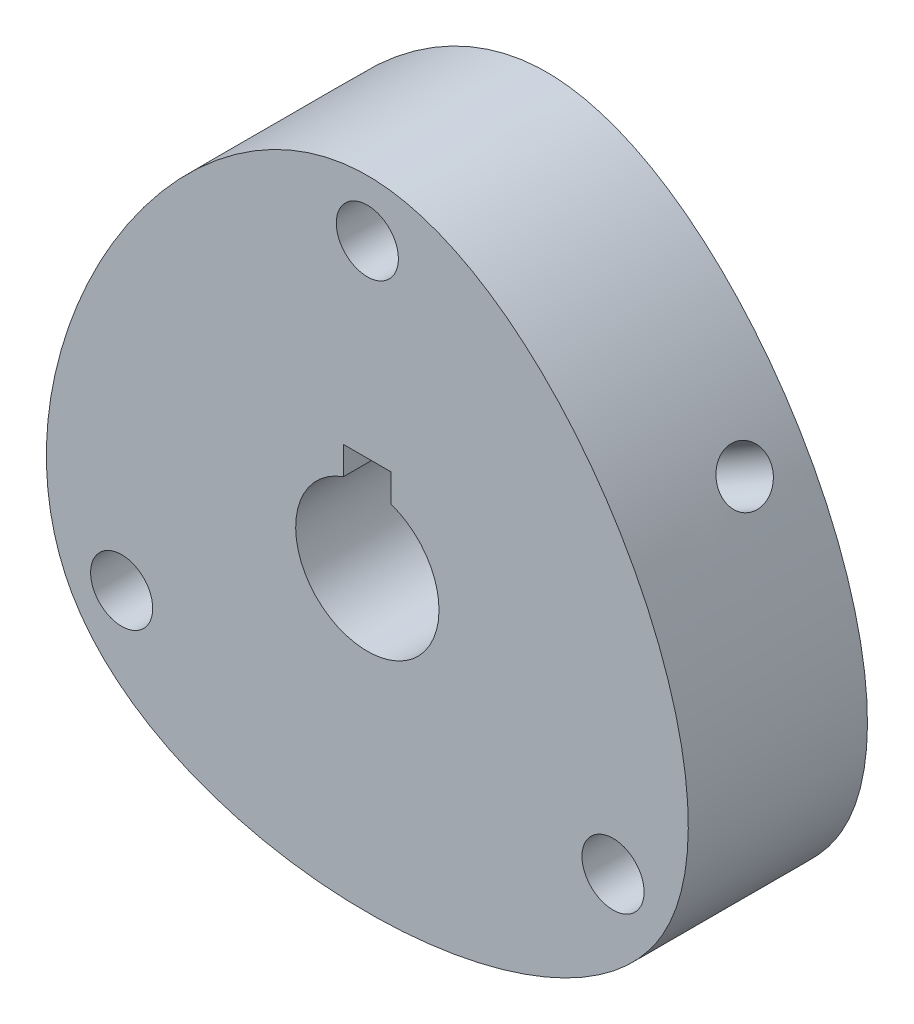
SolidWorks part; units mm, degrees
ref_plane "正面" through (0, 0, 0) normal (0, 0, 1) x (1, 0, 0)
ref_plane "平面" through (0, 0, 0) normal (0, 1, 0) x (1, 0, 0)
ref_plane "右側面" through (0, 0, 0) normal (1, 0, 0) x (0, 0, -1)
sketch "ｽｹｯﾁ1" plane through (0, 0, 0) normal (0, 0, 1) x (1, 0, 0)
  line L0 (0, 0) -> (-20.5681, -11.875) construction
  line L1 (0, 23.75) -> (-20.5681, -11.875) construction
  line L2 (-20.5681, -11.875) -> (20.5681, -11.875) construction
  line L3 (20.5681, -11.875) -> (0, 23.75) construction
  line L14 (-2, 4) -> (2, 4)
  line L15 (-2, 4) -> (-2, 8)
  line L16 (-2, 8) -> (2, 8)
  line L17 (2, 4) -> (2, 8)
  line L18 (-2, 4) -> (2, 8) construction
  line L19 (-2, 8) -> (2, 4) construction
  circle A0 centre (0, 0) radius 11.875 construction
  circle A1 centre (0, 23.75) radius 2.6
  circle A2 centre (20.5681, -11.875) radius 2.6
  circle A3 centre (-20.5681, -11.875) radius 2.6
  circle A4 centre (0, 0) radius 6
  circle A5 centre (0, 0) radius 28.5 construction
  ellipse E0 centre (20.5681, -11.875) end of major axis (23.0681, -7.5449) minor radius 4.75
  ellipse E1 centre (-20.5681, -11.875) end of major axis (-18.0681, -16.2051) minor radius 4.75
  ellipse E2 centre (0, 23.75) end of major axis (5, 23.75) minor radius 4.75
  spline S1 degree 3 poles (-49.3634, -28.5) (49.3634, -28.5) (0, 57) (-49.3634, -28.5) (49.3634, -28.5) (0, 57) knots -1 -0.666667 -0.333333 0 0.333333 0.666667 1 1.333333 1.666667 2 only from (24.6817, -14.25) to (24.6817, -14.25)
  point P26 (0, -5.7735)
  point P31 (0, 6)
  dimension "D1" = 5.2
  dimension "D2" = 5.2
  dimension "D3" = 5.2
  dimension "D5" = 12
  dimension "D6" = 57
  dimension "D4" = 23.75
  dimension "D8" = 4
  dimension "D9" = 4
extrude "ﾎﾞｽ - 押し出し1" add sketch "ｽｹｯﾁ1" along normal blind 15 contours E0 S1 E2 E1 A4 L15 L16 L17 | E0 A2 | E2 A1 | E1 A3 region at (-19.4081, -7.2836, 0) region at (3.3962, 27.0503, 0) region at (0, -24.1796, 0) region at (25.1244, -10.5839, 0)
sketch "ｽｹｯﾁ13" plane through (0, 0, 0) normal (0, 1, 0) x (1, 0, 0)
  line L0 (26.8701, 0) -> (-26.8701, 0) construction
  circle A0 centre (0, -5) radius 2.15
  dimension "D1" = 5
  dimension "D2" = 4.3
extrude "ｶｯﾄ - 押し出し10" cut sketch "ｽｹｯﾁ13" against normal through all
ref_axis "軸1" through (0, 0, 0) along (0, 0, 1)
ref_plane "平面1" through (0, 0, 0) normal (-0.866, -0.5, 0) x (0, 0, 1)
sketch "ｽｹｯﾁ14" plane through (0, 0, 0) normal (-0.866, -0.5, 0) x (0, 0, 1)
  line L0 (0, 26.8701) -> (0, -26.8701) construction
  circle A0 centre (5, 0) radius 2.15
  dimension "D1" = 5
  dimension "D2" = 4.3
extrude "ｶｯﾄ - 押し出し11" cut sketch "ｽｹｯﾁ14" against normal through all
sketch "ｽｹｯﾁ15" plane through (0, 0, 0) normal (0, 0, -1) x (-1, 0, 0)
  circle A0 centre (-20.5681, -11.875) radius 4.1
  circle A1 centre (0, 23.75) radius 4.1
  circle A2 centre (20.5681, -11.875) radius 4.1
  dimension "D1" = 8.2
  dimension "D2" = 8.2
  dimension "D3" = 8.2
extrude "ｶｯﾄ - 押し出し12" cut sketch "ｽｹｯﾁ15" against normal blind 5.2
